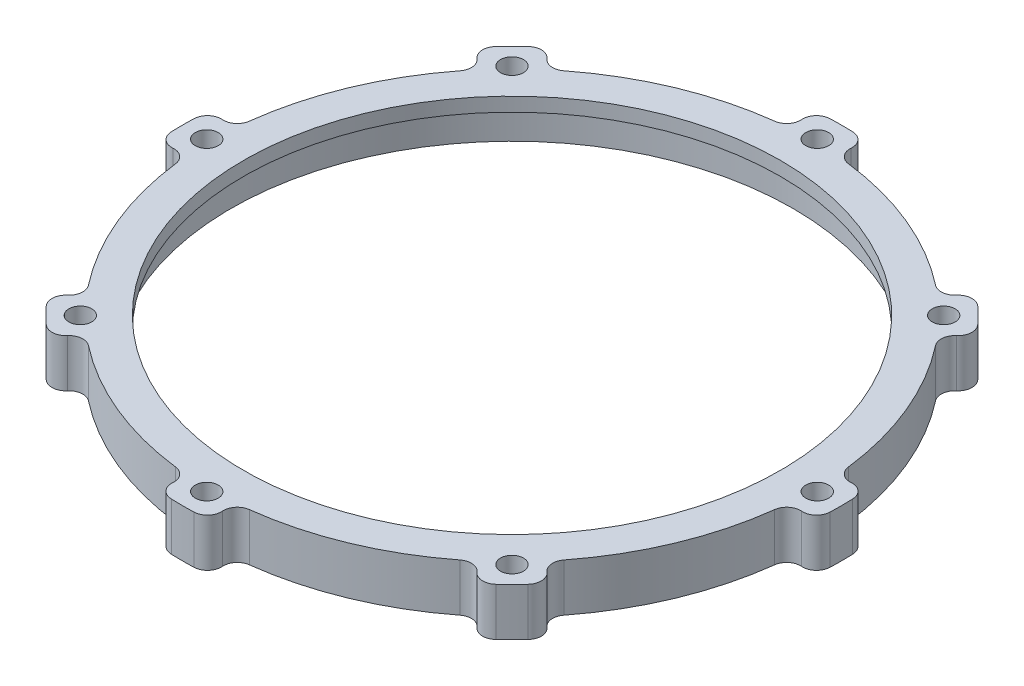
SolidWorks part; units mm, degrees
material "6061-T6 (SS)"
ref_plane "前视基准面" through (0, 0, 0) normal (0, 0, 1) x (1, 0, 0)
ref_plane "上视基准面" through (0, 0, 0) normal (0, 1, 0) x (1, 0, 0)
ref_plane "右视基准面" through (0, 0, 0) normal (1, 0, 0) x (0, 0, -1)
sketch "草图1" plane through (0, 0, 0) normal (0, 0, 1) x (1, 0, 0)
  line L0 (0, 0) -> (0, 34.9743) construction
  line L1 (-40.5, 0) -> (-47.5, 0)
  line L2 (-47.5, 0) -> (-47.5, 6.9)
  line L3 (-47.5, 6.9) -> (-38.7, 6.9)
  line L4 (-38.7, 6.9) -> (-38.7, 4.9)
  line L5 (-38.7, 4.9) -> (-40.5, 4.9)
  line L6 (-40.5, 4.9) -> (-40.5, 0)
  dimension "D1" = 81
  dimension "D2" = 2
  dimension "D3" = 1.8
  dimension "D4" = 4.9
  dimension "D5" = 7
revolve "旋转1" add sketch "草图1" angle 360 about L0
sketch "草图2" plane through (0, 0, 0) normal (0, -1, 0) x (1, 0, 0)
  circle A0 centre (0, 0) radius 44 construction
  circle A1 centre (0, 0) radius 40.5 construction
  circle A2 centre (0, 44) radius 2
  dimension "D1" = 3.5
  dimension "D2" = 4
hole_wizard "M4 螺纹孔1" positions "草图3" profile "草图4" tap size "M4" standard "GB"
sketch "草图3" plane through (0, 0, 0) normal (0, -1, 0) x (-1, 0, 0)
  point P0 (0, -44)
cosmetic thread "孔螺蚊线1" parameters "D1"=8, "D2"=4
sketch "草图4" plane through (0, 0, 44) normal (1, 0, 0) x (0, 0, -1)
  line L0 (0, 0) -> (0, 8.9914)
  line L1 (0, 8.9914) -> (1.65, 8)
  line L2 (1.65, 8) -> (1.65, 0)
  line L5 (1.65, 0) -> (0, 0)
  line L10 (0, 8.9914) -> (-1.65, 8) construction
  line L11 (0, -6.35) -> (0, 107.95) construction
  dimension "螺纹孔钻头直径" = 3.3
  dimension "螺纹孔钻头深度" = 8
  dimension "导头角度" = 118
pattern_circular "阵列(圆周)1" count 8 over 360 about axis through (0, 0, 0) along (0, -1, 0) of "M4 螺纹孔1"
sketch "草图5" plane through (0, 0, 0) normal (0, -1, 0) x (1, 0, 0)
  line L0 (0, 47.5) -> (0, 0) construction
  line L1 (0, 0) -> (-31.1127, 31.1127) construction
  line L2 (0, 0) -> (-30.8488, 36.1193)
  line L3 (-3.7268, 47.3536) -> (0, 0)
  circle A9 centre (0, 0) radius 47.5 construction
  circle A13 centre (0, 0) radius 47.5
  circle A14 centre (0, 0) radius 43.5
  circle A15 centre (0, 0) radius 40.5 construction
  circle M19 centre (0, 0) radius 47.5
  dimension "D1" = 3
  dimension "D2" = 4.5
  dimension "D3" = 4.5
extrude "切除-拉伸1" cut sketch "草图5" against normal blind 10 contours A14 L3 L2 M19 region at (-17.1381, 0, 41.3751)
pattern_circular "阵列(圆周)2" count 8 over 360 about axis through (0, 0, 0) along (0, -1, 0) of "切除-拉伸1"
fillet "圆角2" radius 2 32 edges at (-3.413, 3.45, 43.3659) (-28.251, 3.45, 33.0777) (-30.8488, 3.45, 36.1193) (-36.1193, 3.45, 30.8488) (-33.0777, 3.45, 28.251) (-43.3659, 3.45, 3.413) (-47.3536, 3.45, 3.7268) (-47.3536, 3.45, -3.7268) (-43.3659, 3.45, -3.413) (-33.0777, 3.45, -28.251) (-36.1193, 3.45, -30.8488) (-30.8488, 3.45, -36.1193) (-28.251, 3.45, -33.0777) (-3.413, 3.45, -43.3659) (-3.7268, 3.45, -47.3536) (3.7268, 3.45, -47.3536) (3.413, 3.45, -43.3659) (28.251, 3.45, -33.0777) (30.8488, 3.45, -36.1193) (36.1193, 3.45, -30.8488) (33.0777, 3.45, -28.251) (43.3659, 3.45, -3.413) (47.3536, 3.45, -3.7268) (47.3536, 3.45, 3.7268) (43.3659, 3.45, 3.413) (33.0777, 3.45, 28.251) (36.1193, 3.45, 30.8488) (30.8488, 3.45, 36.1193) (28.251, 3.45, 33.0777) (3.413, 3.45, 43.3659) (3.7268, 3.45, 47.3536) (-3.7268, 3.45, 47.3536)
